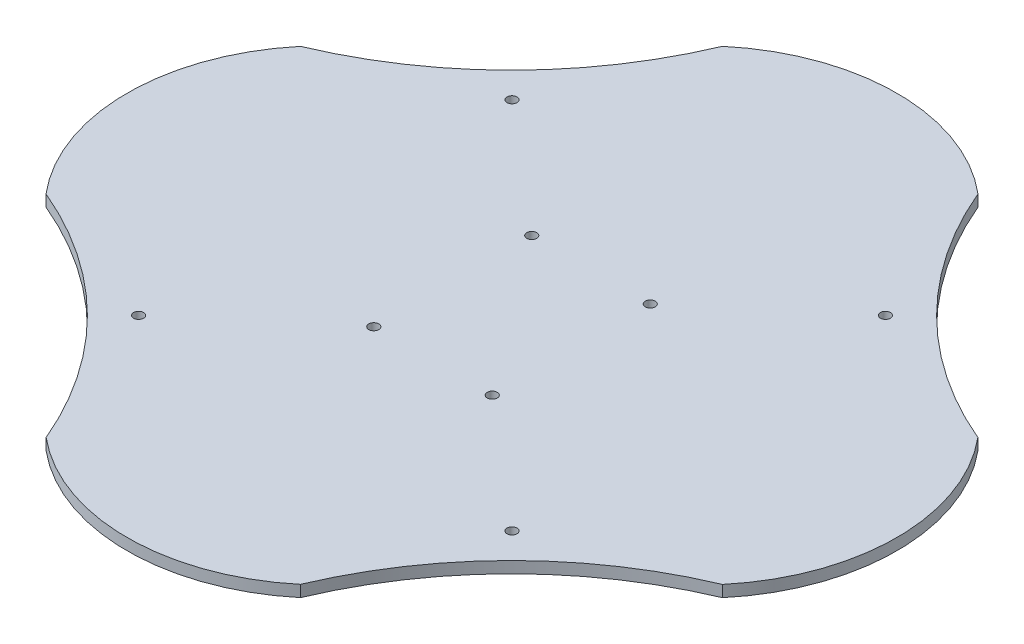
SolidWorks part; units mm, degrees
material "Thornel Mat VMA"
ref_plane "前视基准面" through (0, 0, 0) normal (0, 0, 1) x (1, 0, 0)
ref_plane "上视基准面" through (0, 0, 0) normal (0, 1, 0) x (1, 0, 0)
ref_plane "右视基准面" through (0, 0, 0) normal (1, 0, 0) x (0, 0, -1)
sketch "草图2" plane through (0, 0, 0) normal (0, 1, 0) x (1, 0, 0)
  line L0 (6.6365, 27.504) -> (-106.8107, -85.9432)
  line L1 (-106.8107, 27.504) -> (6.6365, 27.504)
  line L2 (-106.8107, 27.504) -> (-106.8107, -85.9432)
  line L3 (-106.8107, -85.9432) -> (6.6365, -85.9432)
  line L4 (6.6365, 27.504) -> (6.6365, -85.9432)
  line L5 (-106.8107, 27.504) -> (6.6365, -85.9432) construction
  line L6 (-106.8107, -85.9432) -> (6.6365, 27.504) construction
  line L7 (6.6365, -85.9432) -> (-106.8107, 27.504)
  line L8 (-50.0871, -85.9432) -> (-50.0871, -29.2196)
  line L9 (6.6365, -85.9432) -> (99.1639, -178.6774)
  line L10 (99.1639, -178.6774) -> (-199.5448, -178.4707)
  line L11 (-199.5448, -178.4707) -> (-199.3381, 120.2381)
  line L12 (-199.3381, 120.2381) -> (99.3707, 120.0314)
  line L13 (99.3707, 120.0314) -> (99.1639, -178.6774)
  line L14 (6.6365, 27.504) -> (6.6365, 31.004)
  line L15 (-106.8107, 27.504) -> (-106.8107, 31.004)
  line L16 (-106.8107, -85.9432) -> (-110.3107, -85.9432)
  line L17 (6.6365, -85.9432) -> (10.1365, -85.9432)
  line L18 (6.6365, 27.504) -> (10.1365, 27.504)
  arc A0 (-20.836, -178.5943) -> (99.247, -58.6774) centre (99.1639, -178.6774) cw
  arc A1 (-79.3381, -178.5943) -> (-199.4212, -58.6774) centre (-199.3381, -178.6774) ccw
  arc A2 (99.2876, 0.0314) -> (-20.6293, 120.1144) centre (99.3707, 120.0314) cw
  arc A3 (-199.4618, 0.0314) -> (-79.5449, 120.1144) centre (-199.5448, 120.0314) ccw
  circle A4 centre (6.6365, -85.9432) radius 3.5
  circle A5 centre (6.6365, 27.504) radius 3.5
  circle A6 centre (-106.8107, -85.9432) radius 3.5
  arc A7 (-110.3107, -85.9432) -> (10.1365, -85.9432) centre (-50.0871, -85.9432) ccw
  arc A8 (6.6365, -89.4432) -> (6.6365, 31.004) centre (6.6365, -29.2196) ccw
  arc A9 (-106.8107, -89.4432) -> (-106.8107, 31.004) centre (-106.8107, -29.2196) cw
  arc A10 (-110.3107, 27.504) -> (10.1365, 27.504) centre (-50.0871, 27.504) cw
  circle A11 centre (-106.8107, 27.504) radius 3.5
  circle A12 centre (-106.8107, -85.9432) radius 1.52
  circle A13 centre (6.6365, -85.9432) radius 1.52
  circle A14 centre (6.6365, 27.504) radius 1.52
  circle A15 centre (-106.8107, 27.504) radius 1.52
  point P0 (-50.0871, -29.2196)
  dimension "D2" = 3.5
  dimension "D3" = 3.5
  dimension "D4" = 3.5
extrude "凸台-拉伸3" add sketch "草图2" along normal blind 3.5 contours A11 A10 A9 A3 A1 A7 A6 L2 | A11 L2 A6 L0 L7 | A6 L3 L8 L0 | A4 L7 L8 L3 | A6 A9 A7 A1 A0 L9 A8 A4 L3 | A5 L0 L7 A4 L4 | A11 L1 A5 A8 A10 A2 A3 A9 | A9 A10 A3 | A9 A6 A7 | A12 L3 A6 L0 | A12 L0 A6 L2 | A11 A9 A10 | A15 L1 A11 L2 | A15 L7 A11 L1 | A10 A8 A5 | A8 A10 A5 L4 A4 A7 A0 A2 | A2 A10 A8 | A7 A0 L9 | A8 A7 L9 A0 | A13 L3 A4 L9 | A4 A8 L9 | L9 A8 A7 A4 | A13 L4 A4 L7 | A13 L7 A4 L3 | A12 L2 A6 L16 | A13 L9 A4 L17 | A15 L1 A11 L15 | A13 L17 A4 L4 | A11 L7 L0 A5 L1 | A14 L14 A5 L1 | A14 L18 A5 L14 | A14 L4 A5 L18 | A14 L0 A5 L4 | A14 L1 A5 L0 | A12 L16 A6 L3 | A15 L2 A11 L7 | A7 A9 A1 region at (5.6519, 0, -25.127) region at (4.2595, 0, -26.5194) region at (4.9557, 0, -29.1848) region at (8.3173, 0, -25.8232) region at (8.3173, 0, -29.1848) region at (-12.3254, 0, 29.2196) region at (-50.0871, 0, -8.542) region at (-50.0871, 0, -53.0541) region at (32.1831, 0, 29.2407) region at (9.3252, 0, -30.1926) region at (-68.8878, 0, 66.9813) region at (-87.8487, 0, 29.2196) region at (-31.2863, 0, 66.9813) region at (-104.4337, 0, -26.5194) region at (-105.1299, 0, -29.1848) region at (8.3173, 0, 84.2625) region at (5.6519, 0, 83.5663) region at (13.0427, 0, -33.9258) region at (-104.4337, 0, 84.9587) region at (-105.8261, 0, 83.5663) region at (4.2595, 0, 84.9587) region at (-105.8261, 0, -25.127) region at (-50.0871, 0, 111.4863) region at (-109.4994, 0, -30.1926) region at (-108.4915, 0, -27.504) region at (9.0128, 0, 86.9291) region at (9.793, 0, 88.1669) region at (-106.8107, 0, 87.624) region at (-132.3573, 0, 29.2407) region at (-108.4915, 0, 84.2625) region at (5.8429, 0, 87.8561) region at (-113.2169, 0, -33.9258) region at (8.8526, 0, 89.1017) region at (15.0288, 0, 90.3822) region at (-109.4994, 0, 88.6319) region at (11.0717, 0, 94.3328) region at (-113.2325, 0, 92.3494)
sketch "草图4" plane through (0, 7.25, 0) normal (0, -1, 0) x (1, 0, 0)
  circle A0 centre (-68.0871, 5.2196) radius 1.52
  circle A1 centre (-32.0871, 5.2196) radius 1.52
  circle A2 centre (-68.0871, 53.2196) radius 1.52
  circle A3 centre (-32.0871, 53.2196) radius 1.52
extrude "切除-拉伸2" cut sketch "草图4" along normal blind 59
